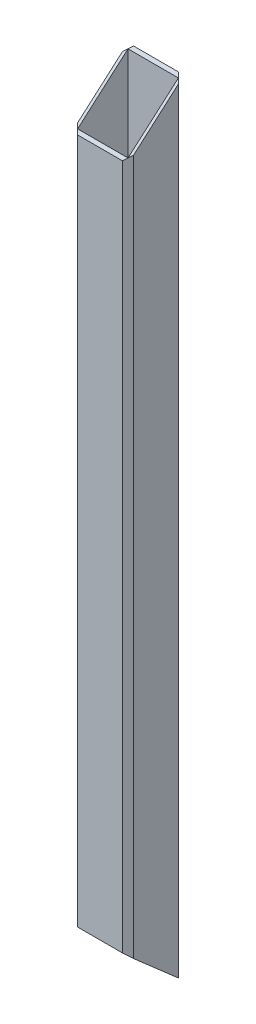
SolidWorks part; units mm, degrees
ref_plane "Front Plane" through (0, 0, 0) normal (0, 0, 1) x (1, 0, 0)
ref_plane "Top Plane" through (0, 0, 0) normal (0, 1, 0) x (1, 0, 0)
ref_plane "Right Plane" through (0, 0, 0) normal (1, 0, 0) x (0, 0, -1)
sketch "Sketch1" plane through (0, 0, 0) normal (0, 0, 1) x (1, 0, 0)
  line L1 (0, 0) -> (50, 0)
  line L2 (0, 0) -> (0, 700)
  line L3 (0, 700) -> (50, 700)
  line L4 (50, 0) -> (50, 700)
  dimension "D1" = 50
  dimension "D2" = 700
extrude "Boss-Extrude1" add sketch "Sketch1" along normal blind 50 contours L2 L1 L4 L3
sketch "Sketch2" plane through (0, 700, 0) normal (0, 1, 0) x (1, 0, 0)
  line L0 (2.5, -2.5) -> (47.5, -2.5)
  line L2 (0, 0) -> (50, 0) construction
  line L3 (47.5, -2.5) -> (47.5, -47.5)
  line L4 (47.5, -47.5) -> (2.5, -47.5)
  line L5 (2.5, -47.5) -> (2.5, -2.5)
  line L6 (0, -50) -> (50, -50) construction
  line L8 (50, -50) -> (50, 0) construction
  line L9 (0, -50) -> (0, 0) construction
  dimension "D1" = 2.5
  dimension "D2" = 2.5
  dimension "D3" = 2.5
  dimension "D4" = 2.5
extrude "Cut-Extrude1" cut sketch "Sketch2" against normal through all contours L0 L3 L4 L5
sketch "Sketch3" plane through (0, 0, 0) normal (-1, 0, 0) x (0, 0, 1)
  line L0 (0, 700) -> (50, 700)
  line L1 (50, 700) -> (50, 656.25)
  line L2 (50, 0) -> (50, 700) construction
  line L3 (50, 656.25) -> (0, 700)
  line L4 (0, 0) -> (50, 0)
  line L5 (50, 0) -> (50, 43.75)
  line L6 (50, 43.75) -> (0, 0)
extrude "Cut-Extrude2" cut sketch "Sketch3" against normal through all contours L3 L0 L1 | L6 L4 L5
chamfer "Chamfer1" distance 5 angle 45 4 edges at (0, 350, 0) (0, 350, 50) (50, 350, 0) (50, 350, 50)
